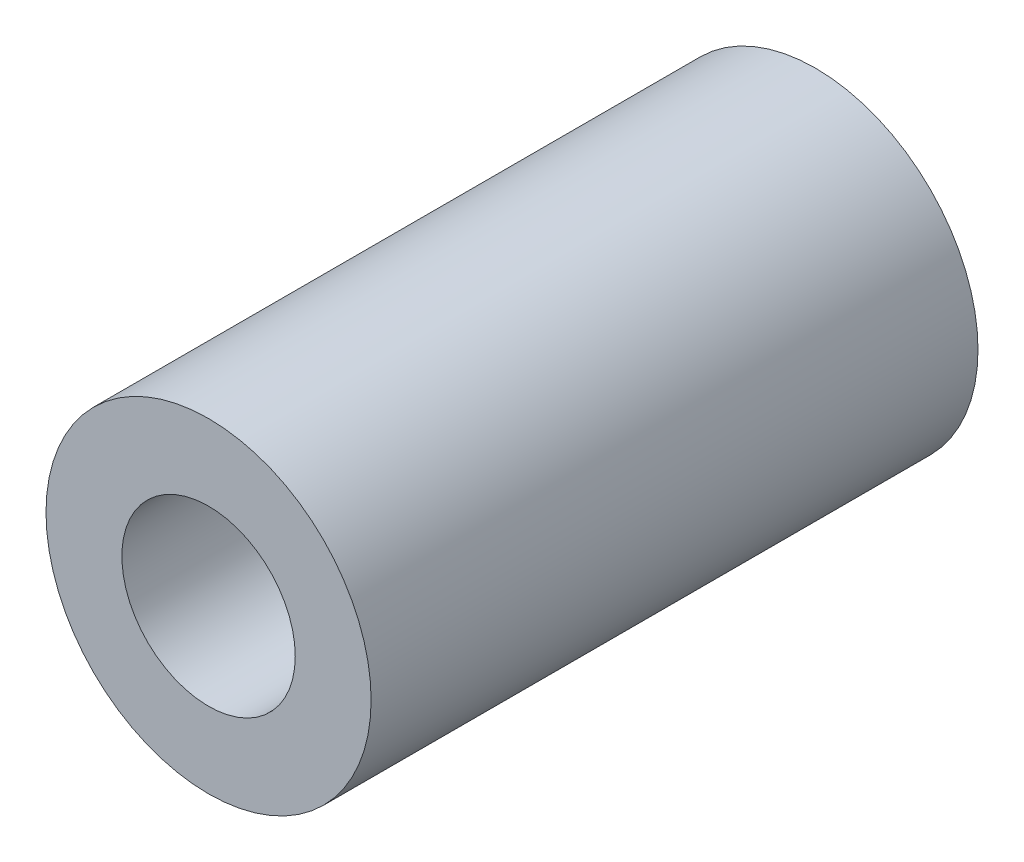
SolidWorks part; units mm, degrees
ref_plane "Front Plane" through (0, 0, 0) normal (0, 0, 1) x (1, 0, 0)
ref_plane "Top Plane" through (0, 0, 0) normal (0, 1, 0) x (1, 0, 0)
ref_plane "Right Plane" through (0, 0, 0) normal (1, 0, 0) x (0, 0, -1)
sketch "Sketch2" plane through (0, 0, 0) normal (0, 0, 1) x (1, 0, 0)
  line L0 (4, -96.0002) -> (9.6569, -90.3433) construction
  line L2 (1.3484, -93.3485) -> (7.0052, -87.6917)
  line L3 (6.6517, -98.6518) -> (12.3085, -92.995)
  arc A0 (1.3484, -93.3485) -> (6.6517, -98.6518) centre (4, -96.0002) ccw
  arc A1 (12.3085, -92.995) -> (7.0052, -87.6917) centre (9.6569, -90.3433) ccw
  circle A2 centre (9.6569, -90.3433) radius 2
  dimension "D3" = 7.5
  dimension "D4" = 4
  dimension "D2" = 8
extrude "Boss-Extrude1" add sketch "Sketch2" along normal blind 4
sketch "Sketch3" plane through (0, 0, 4) normal (0, 0, 1) x (1, 0, 0)
  circle A0 centre (4, -96.0002) radius 2
  dimension "D1" = 4
extrude "Cut-Extrude1" cut sketch "Sketch3" against normal blind 4
sketch "Sketch4" plane through (0, 0, 4) normal (0, 0, 1) x (1, 0, 0)
  circle A0 centre (4, -96.0002) radius 3
  dimension "D1" = 6
extrude "Cut-Extrude2" cut sketch "Sketch4" against normal blind 2
sketch "Sketch5" plane through (0, 0, 4) normal (0, 0, 1) x (1, 0, 0)
  circle A0 centre (9.6569, -90.3433) radius 3.75
  circle A1 centre (9.6569, -90.3433) radius 2
extrude "Boss-Extrude2" add sketch "Sketch5" along normal blind 10
